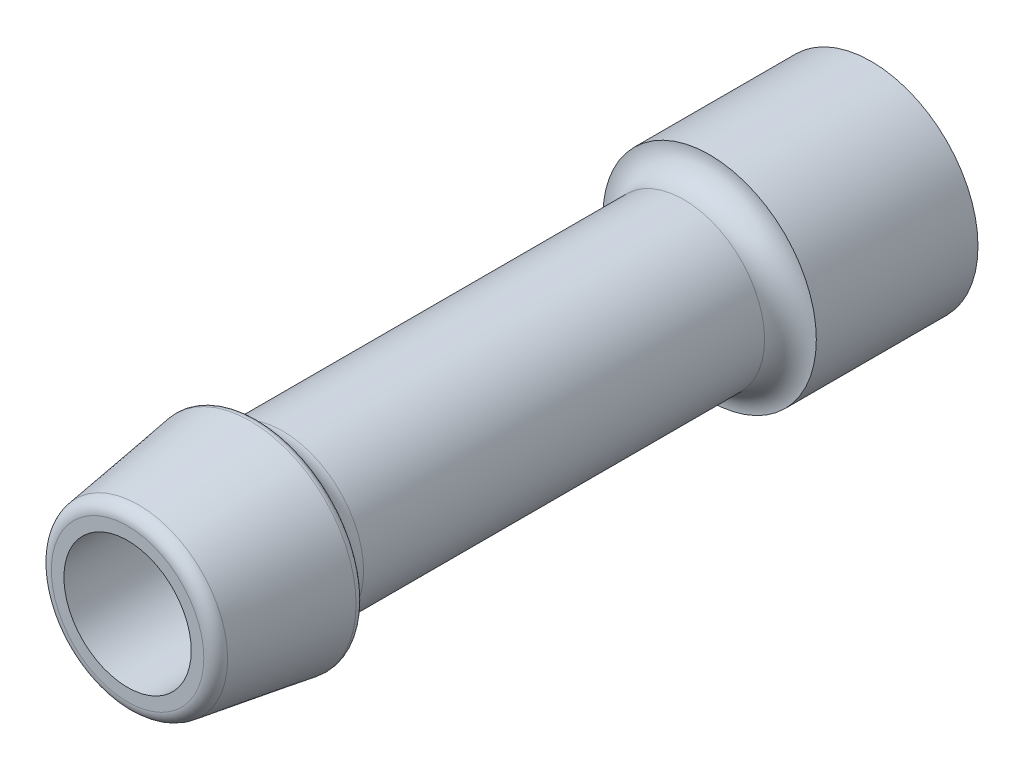
SolidWorks part; units mm, degrees
material "Custom Plastic"
ref_plane "X-Y Datum" through (0, 0, 0) normal (0, 0, 1) x (1, 0, 0)
ref_plane "X-Z Datum" through (0, 0, 0) normal (0, 1, 0) x (1, 0, 0)
ref_plane "Y-Z Datum" through (0, 0, 0) normal (1, 0, 0) x (0, 0, -1)
sketch "Sketch1" plane through (0, 0, 0) normal (0, 0, 1) x (1, 0, 0)
  circle A0 centre (0, 0) radius 4.191
  dimension "D1" = 8.382
extrude "Boss-Extrude1" add sketch "Sketch1" along normal blind 29.21
sketch3d "3DSketch1"
  line L0 (0, 0, 29.21) -> (0, 0, 0)
  line L1 (0, 0, 29.21) -> (0, 0, 0) construction
sketch "Sketch2" plane through (0, 0, 29.21) normal (0, 0, 1) x (1, 0, 0)
  circle A0 centre (0, 0) radius 2.5
  dimension "D1" = 5
sweep "Cut-Sweep1" cut profiles "Sketch2" path "3DSketch1"
sketch "Sketch3" plane through (0, 0, 29.21) normal (0, 0, 1) x (1, 0, 0)
  circle A0 centre (0, 0) radius 3.175
  circle A1 centre (0, 0) radius 5.08
extrude "Cut-Extrude1" cut sketch "Sketch3" against normal blind 17.78 from offset 5.08 offset against normal yes
fillet "Fillet1" radius 1.016 1 edges at (3.175, 0, 6.35)
fillet "Fillet2" radius 1.016 1 edges at (3.175, 0, 24.13)
chamfer "Chamfer1" distance 5.08 angle 8.5 1 edges at (4.191, 0, 29.21) first distance on face at (4.191, 0, 24.13)
fillet "Fillet3" radius 0.254 1 edges at (4.191, 0, 24.13)
fillet "Fillet4" radius 0.508 1 edges at (3.4318, 0, 29.21)
